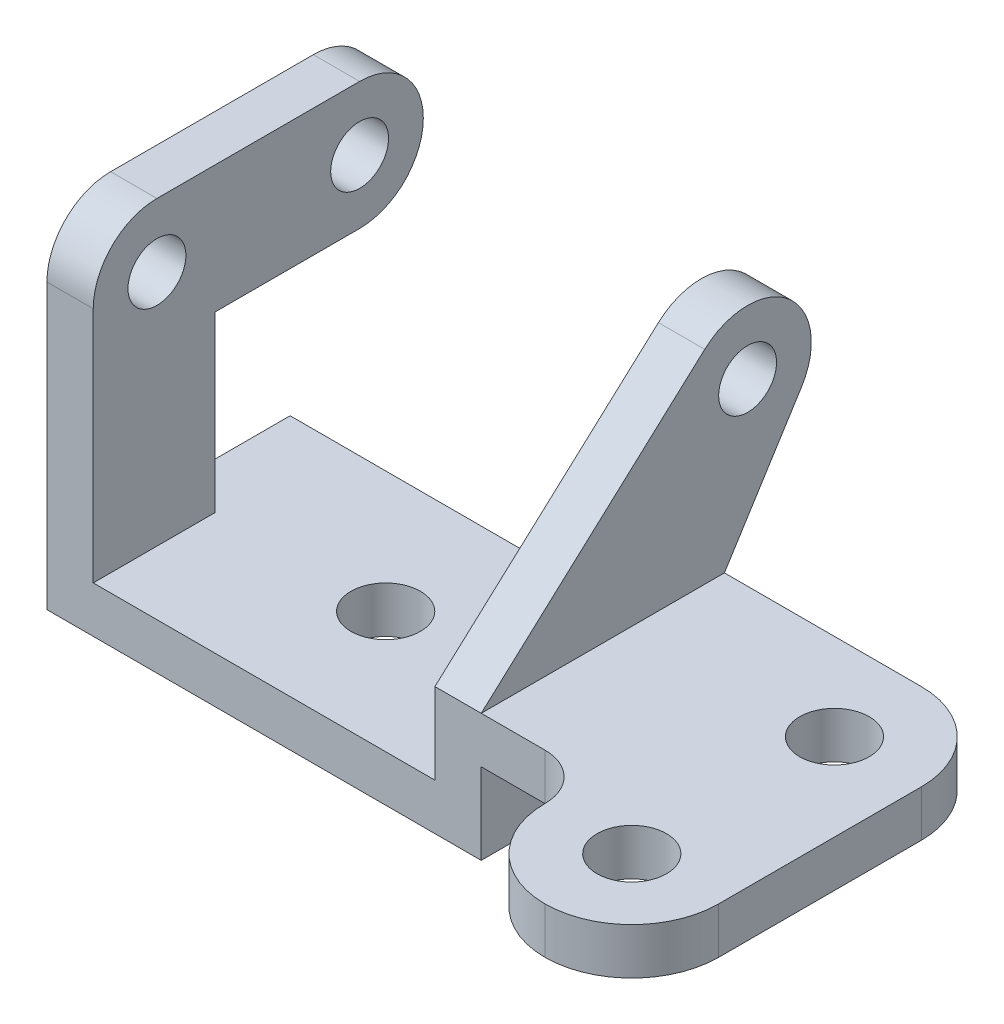
SolidWorks part; units mm, degrees
other "DetailItem1"
other "DetailItem2"
other "DetailItem3"
other "DetailItem4"
other "DetailItem5" parameters "RD1"=28, "RD6"=8, "RD7"=70, "RD9"=82, "RD10"=82, "RD11"=42, "RD12"=59, "RD13"=150, "RD14"=16, "RD15"=42, "RD16"=84, "RD17"=54, "RD18"=70
ref_plane "Front Plane" through (0, 0, 0) normal (0, 0, 1) x (1, 0, 0)
ref_plane "Top Plane" through (0, 0, 0) normal (0, 1, 0) x (1, 0, 0)
ref_plane "Right Plane" through (0, 0, 0) normal (1, 0, 0) x (0, 0, -1)
sketch "Sketch1" plane through (0, 0, 0) normal (0, 1, 0) x (1, 0, 0)
  line L0 (-678.9953, -47.3008) -> (-210.3286, -47.3008) construction
  line L1 (-75, -42) -> (75, -42)
  line L2 (-75, -42) -> (-75, 42)
  line L3 (-75, 42) -> (75, 42)
  line L4 (75, -42) -> (75, 42)
  line L5 (-75, -42) -> (75, 42) construction
  line L6 (-75, 42) -> (75, -42) construction
  circle A0 centre (0, 0) radius 12
  point P0 (0, 0)
  dimension "D1" = 150
  dimension "D2" = 84
extrude "Boss-Extrude1" add sketch "Sketch1" along normal blind 16
sketch "Sketch4" plane through (0, 16, 0) normal (0, 1, 0) x (1, 0, 0)
  line L5 (75, 42) -> (-75, 42) construction
  line L6 (75, -42) -> (59, -42)
  line L7 (75, -42) -> (75, 42)
  line L8 (75, 42) -> (59, 42)
  line L9 (59, -42) -> (59, 42)
  dimension "D1" = 16
extrude "Boss-Extrude2" add sketch "Sketch4" along normal blind 28
sketch "Sketch5" plane through (75, 0, 0) normal (1, 0, 0) x (0, 0, -1)
  line L0 (42, 44) -> (42, 0) construction
  line L1 (-42, 44) -> (42, 44)
  line L2 (-42, 44) -> (-42, 28)
  line L3 (-42, 28) -> (42, 28)
  line L4 (42, 44) -> (42, 28)
  dimension "D1" = 16
extrude "Boss-Extrude3" add sketch "Sketch5" along normal blind 98
sketch "Sketch7" plane through (0, 0, 42) normal (0, 0, 1) x (1, 0, 0)
  line L0 (59, 44) -> (173, 44) construction
  line L1 (173, 28) -> (113, 28)
  line L2 (173, 28) -> (173, 44)
  line L3 (173, 44) -> (113, 44)
  line L4 (113, 28) -> (113, 44)
  dimension "D1" = 60
extrude "Boss-Extrude4" add sketch "Sketch7" along normal blind 46
fillet "Fillet2" radius 30 3 edges at (173, 36, 88) (173, 36, -42) (113, 36, 88)
fillet "Fillet3" radius 16 1 edges at (113, 36, 42)
sketch "Sketch9" plane through (0, 44, 0) normal (0, 1, 0) x (1, 0, 0)
  line L0 (143, 42) -> (143, -88) construction
  line L1 (113, -58) -> (173, -58) construction
  line L2 (97, -42) -> (173, -42) construction
  line L3 (173, 12) -> (173, -58) construction
  line L4 (173, 12) -> (113, 12) construction
  circle A0 centre (143, 12) radius 12
  circle A1 centre (143, -58) radius 12
  dimension "D1" = 16
  dimension "D2" = 70
  dimension "D3" = 54
extrude "Cut-Extrude1" cut sketch "Sketch9" against normal up to next
sketch "Sketch11" plane through (59, 0, 0) normal (-1, 0, 0) x (0, 0, 1)
  line L0 (-72, 98) -> (42, 98) construction
  line L9 (-50, 120) -> (-50, 76) construction
  line L10 (-42, 118.4939) -> (-42, 120) construction
  line L11 (-42, 44) -> (-68.6176, 86.2789)
  line L12 (42, 44) -> (-35.1902, 114.2686)
  line L13 (-42, 44) -> (42, 44)
  arc A1 (-35.1902, 114.2686) -> (-68.6176, 86.2789) centre (-50, 98) ccw
  circle A2 centre (-50, 98) radius 10
  point P11 (-72, 120)
  dimension "D7" = 22
  dimension "D8" = 20
  dimension "D2" = 30
  dimension "D4" = 8
  dimension "D6" = 8
extrude "Boss-Extrude5" add sketch "Sketch11" against normal blind 16
sketch "Sketch13" plane through (0, 16, 0) normal (0, 1, 0) x (1, 0, 0)
  line L0 (-24.2, 0) -> (24.2, 0) construction
  line L1 (-75, -42) -> (-59, -42)
  line L2 (-75, -42) -> (-75, 0)
  line L3 (-75, 0) -> (-59, 0)
  line L4 (-59, -42) -> (-59, 0)
  dimension "D1" = 16
extrude "Boss-Extrude6" add sketch "Sketch13" along normal blind 104
sketch "Sketch14" plane through (0, 0, 0) normal (0, 0, -1) x (-1, 0, 0)
  line L0 (75, 120) -> (75, 16) construction
  line L1 (59, 120) -> (75, 120)
  line L2 (59, 120) -> (59, 76)
  line L3 (59, 76) -> (75, 76)
  line L4 (75, 120) -> (75, 76)
  dimension "D1" = 44
fillet "Fillet4" radius 22 1 edges at (-67, 120, 42)
sketch "Sketch15" plane through (-75, 0, 0) normal (-1, 0, 0) x (0, 0, 1)
  line L0 (42, 98) -> (20, 98) construction
  line L1 (20, 120) -> (20, 98) construction
  line L2 (20, 98) -> (-72, 98) construction
  line L3 (20, 98) -> (-50, 98) construction
  circle A0 centre (20, 98) radius 10
  arc A1 (-35.1902, 114.2686) -> (-68.6176, 86.2789) centre (-50, 98) ccw construction
extrude "Cut-Extrude2" cut sketch "Sketch15" against normal up to next
extrude "Boss-Extrude8" add sketch "Sketch14" along normal blind 72
sketch "Sketch16" plane through (-75, 0, 0) normal (-1, 0, 0) x (0, 0, 1)
  line L0 (20, 98) -> (-72, 98) construction
  line L2 (42, 98) -> (20, 98) construction
  line L3 (-72, 76) -> (-72, 120) construction
  line L4 (20, 98) -> (-50, 98) construction
  circle A0 centre (-50, 98) radius 10
extrude "Cut-Extrude3" cut sketch "Sketch16" against normal up to next
fillet "Fillet5" radius 22 2 edges at (-67, 120, -72) (-67, 76, -72)
